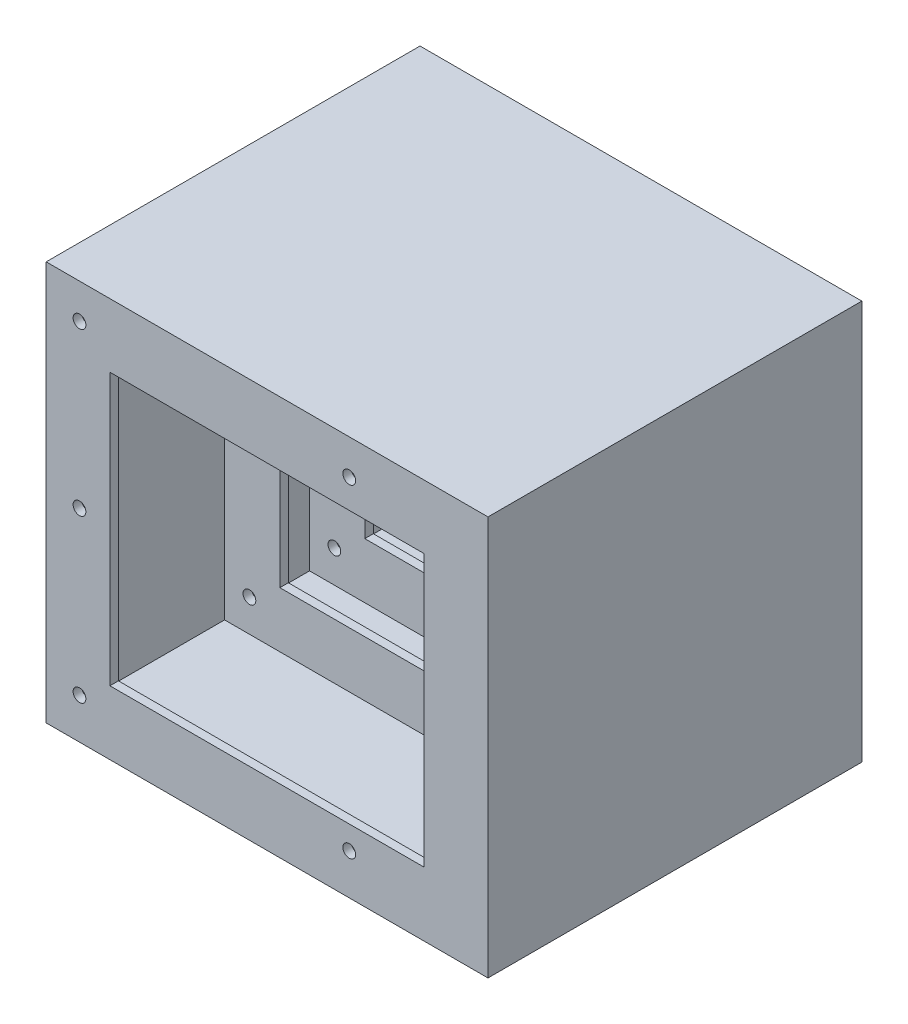
SolidWorks part; units mm, degrees
ref_plane "Front Plane" through (0, 0, 0) normal (0, 0, 1) x (1, 0, 0)
ref_plane "Top Plane" through (0, 0, 0) normal (0, 1, 0) x (1, 0, 0)
ref_plane "Right Plane" through (0, 0, 0) normal (1, 0, 0) x (0, 0, -1)
sketch "Sketch3" plane through (0, 0, 0) normal (0, 0, 1) x (1, 0, 0)
  line L0 (-31.3322, 21.8865) -> (-31.3322, -68.1135)
  line L1 (-31.3322, -68.1135) -> (68.6678, -68.1135)
  line L2 (68.6678, -68.1135) -> (68.6678, 21.8865)
  line L3 (68.6678, 21.8865) -> (-31.3322, 21.8865)
  dimension "D1" = 100
  dimension "D2" = 90
sketch "Sketch5" plane through (0, 0, 0) normal (1, 0, 0) x (0, 0, -1)
extrude "Extrude-Thin1" add sketch "Sketch3" along normal blind 86 thin thin type one direction wall 2
extrude "Boss-Extrude1" add sketch "Sketch3<2>" along normal blind 2
sketch "Sketch3<2>" plane through (0, 0, 0) normal (0, 0, 1) x (1, 0, 0) same geometry as "Sketch3"
sketch "Sketch6" plane through (0, 0, 86) normal (0, 0, 1) x (1, 0, 0)
  line L1 (-33.3322, 23.8865) -> (70.6678, 23.8865)
  line L2 (-33.3322, 23.8865) -> (-33.3322, -70.1135)
  line L3 (-33.3322, -70.1135) -> (70.6678, -70.1135)
  line L4 (70.6678, 23.8865) -> (70.6678, -70.1135)
  line L7 (-18.3322, 8.8865) -> (55.5801, 8.8865)
  line L8 (-18.3322, 8.8865) -> (-18.3322, -55.0404)
  line L9 (-18.3322, -55.0404) -> (55.5801, -55.0404)
  line L10 (55.5801, 8.8865) -> (55.5801, -55.0404)
extrude "Boss-Extrude2" add sketch "Sketch6" along normal blind 2
pattern_linear "LPattern1" count 2 spacing 40 along (0, 0, -1) of "Boss-Extrude2"
pattern_linear "LPattern2" count 2 spacing 60 along (0, 0, -1) of "Boss-Extrude2"
sketch "Sketch9" plane through (0, 0, 88) normal (0, 0, 1) x (1, 0, 0)
  circle A0 centre (-25.4922, 15.6647) radius 1.5
  circle A1 centre (38.0078, 15.6647) radius 1.5
  circle A2 centre (38.0078, -22.4353) radius 1.5
  circle A3 centre (38.0078, -60.5353) radius 1.5
  circle A4 centre (-25.4922, -22.4353) radius 1.5
  circle A5 centre (-25.4922, -60.5353) radius 1.5
  dimension "D1" = 2
  dimension "D2" = 3
extrude "Cut-Extrude1" cut sketch "Sketch9" against normal up to surface (86 mm away) up to face at (18.6678, -23.1135, 2)
sketch "Sketch10" plane through (0, -70.1135, 0) normal (0, -1, 0) x (1, 0, 0)
  line L0 (-14.7915, 69.4536) -> (-14.7915, 29.4536)
  line L1 (-14.7915, 69.4536) -> (3.2085, 69.4536)
  line L2 (3.2085, 69.4536) -> (3.2085, 29.4536)
  line L3 (3.2085, 29.4536) -> (-14.7915, 29.4536)
  line L4 (30.795, 69.4536) -> (30.795, 29.4536)
  line L5 (30.795, 29.4536) -> (48.795, 29.4536)
  line L6 (30.795, 69.4536) -> (48.795, 69.4536)
  line L7 (48.795, 69.4536) -> (48.795, 29.4536)
extrude "Boss-Extrude3" add sketch "Sketch10" along normal blind 8.5
sketch "Sketch12" plane through (48.795, 0, 0) normal (1, 0, 0) x (0, 0, -1)
  line L6 (-29.4536, -70.1135) -> (-69.4536, -70.1135) construction
  line L7 (-66.9536, -70.1135) -> (-31.9536, -70.1135)
  line L8 (-66.9536, -70.1135) -> (-66.9536, -76.1135)
  line L9 (-66.9536, -76.1135) -> (-31.9536, -76.1135)
  line L10 (-31.9536, -70.1135) -> (-31.9536, -76.1135)
extrude "Cut-Extrude2" cut sketch "Sketch12" against normal blind 65.5
